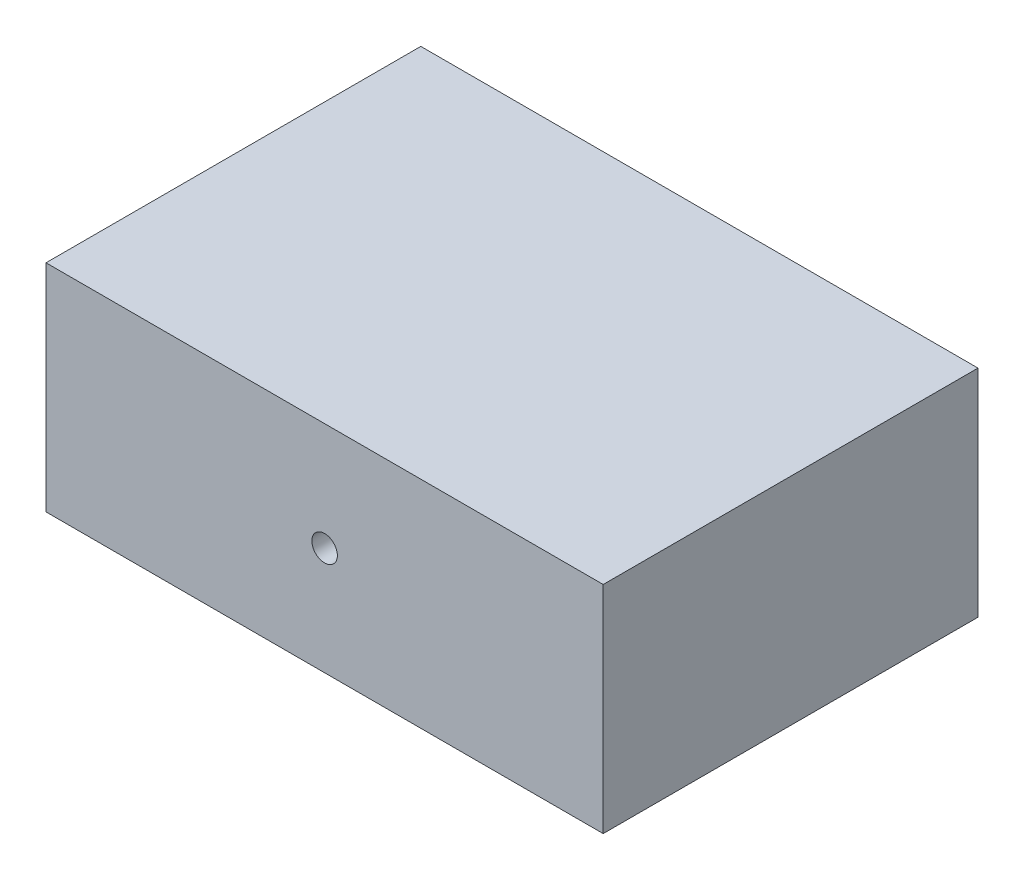
SolidWorks part; units mm, degrees
ref_plane "Front Plane" through (0, 0, 0) normal (0, 0, 1) x (1, 0, 0)
ref_plane "Top Plane" through (0, 0, 0) normal (0, 1, 0) x (1, 0, 0)
ref_plane "Right Plane" through (0, 0, 0) normal (1, 0, 0) x (0, 0, -1)
sketch "Sketch1" plane through (0, 0, 0) normal (0, 1, 0) x (1, 0, 0)
  line L1 (0, 0) -> (111.506, 0)
  line L2 (0, 0) -> (0, 75.0062)
  line L3 (0, 75.0062) -> (111.506, 75.0062)
  line L4 (111.506, 0) -> (111.506, 75.0062)
  dimension "D1" = 111.506
  dimension "D2" = 75.0062
extrude "Boss-Extrude1" add sketch "Sketch1" along normal blind 43.18
sketch "Sketch2" plane through (0, 0, 0) normal (0, 0, 1) x (1, 0, 0)
  line L0 (0, 43.18) -> (111.506, 43.18) construction
  line L2 (0, 43.18) -> (0, 0) construction
  circle A0 centre (55.753, 21.59) radius 3.175
  point P4 (0, 0)
  point P6 (0, 28.8947)
  dimension "D3" = 6.35
  dimension "D1" = 21.59
  dimension "D2" = 55.753
hole_wizard "1/4-20 Tapped Hole1" positions "3DSketch2" profile "Sketch4" tap size "1/4-20" standard "ANSI Inch"
sketch3d "3DSketch2"
  point P0 (55.753, 21.59, 0)
  point P5 (0, 0, 0)
sketch "Sketch4" plane through (55.753, 21.59, 0) normal (1, 0, 0) x (0, -1, 0)
  line L0 (0, 0) -> (0, 18.0438)
  line L1 (0, 18.0438) -> (2.5527, 16.51)
  line L2 (2.5527, 16.51) -> (2.5527, 0)
  line L5 (2.5527, 0) -> (0, 0)
  line L10 (0, 18.0438) -> (-2.5527, 16.51) construction
  line L11 (0, -6.35) -> (0, 107.95) construction
  dimension "Tap Drill Dia." = 5.1054
  dimension "Tap Drill Depth" = 16.51
  dimension "Drill Angle" = 118
cosmetic thread "Hole Thread1" parameters "D1"=12.7, "D2"=6.35
